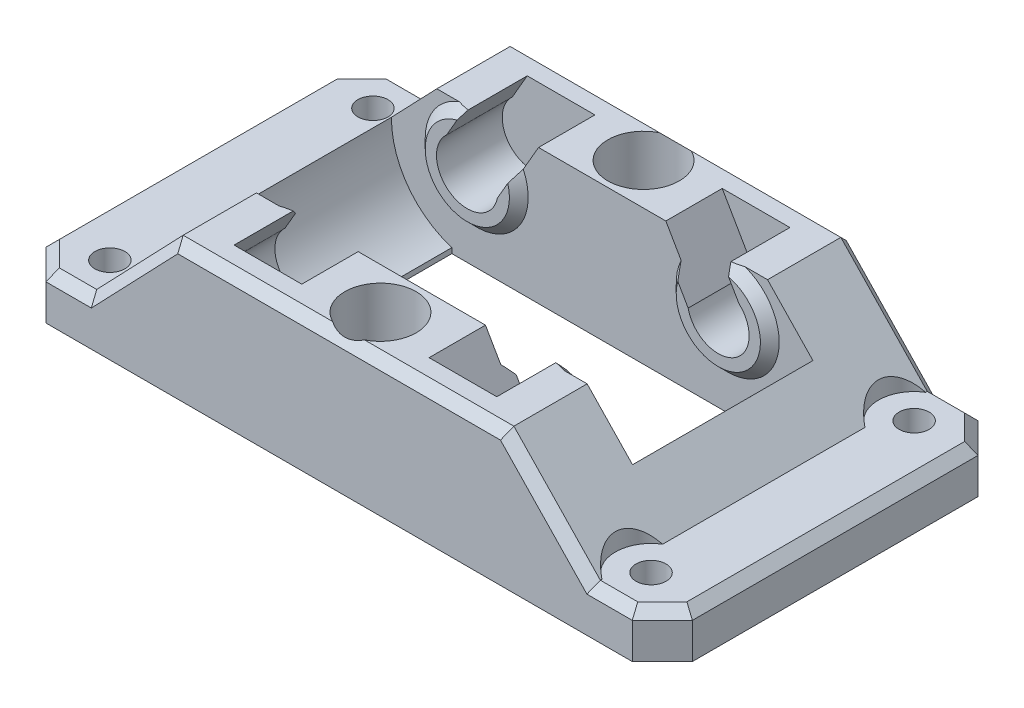
SolidWorks part; units mm, degrees
material "ABS"
ref_plane "Front Plane" through (0, 0, 0) normal (0, 0, 1) x (1, 0, 0)
ref_plane "Top Plane" through (0, 0, 0) normal (0, 1, 0) x (1, 0, 0)
ref_plane "Right Plane" through (0, 0, 0) normal (1, 0, 0) x (0, 0, -1)
sketch "Sketch1" plane through (0, 0, 0) normal (0, 1, 0) x (1, 0, 0)
  line L0 (-39, -23) -> (-43, -19)
  line L1 (39, 23) -> (-39, 23)
  line L2 (43, 19) -> (43, -19)
  line L3 (39, -23) -> (-39, -23)
  line L4 (-43, 19) -> (-43, -19)
  line L5 (43, 23) -> (-43, -23) construction
  line L6 (43, -23) -> (-43, 23) construction
  line L7 (-39, 23) -> (-43, 19)
  line L8 (43, 19) -> (39, 23)
  line L9 (43, -19) -> (39, -23)
  line L11 (36, 17.5) -> (-36, 17.5) construction
  line L12 (36, 17.5) -> (36, -17.5) construction
  line L13 (36, -17.5) -> (-36, -17.5) construction
  line L14 (-36, 17.5) -> (-36, -17.5) construction
  line L15 (36, 17.5) -> (-36, -17.5) construction
  line L16 (36, -17.5) -> (-36, 17.5) construction
  line L17 (20, 12) -> (-20, 12)
  line L18 (20, 12) -> (20, -12)
  line L19 (20, -12) -> (-20, -12)
  line L20 (-20, 12) -> (-20, -12)
  line L21 (20, 12) -> (-20, -12) construction
  line L22 (20, -12) -> (-20, 12) construction
  circle A0 centre (-36, 17.5) radius 2
  circle A1 centre (0, 17.5) radius 2
  circle A2 centre (36, 17.5) radius 2
  circle A3 centre (36, -17.5) radius 2
  circle A4 centre (0, -17.5) radius 2
  circle A5 centre (-36, -17.5) radius 2
  point P0 (0, 0)
  point P14 (0, 0)
  point P27 (0, 0)
  dimension "D9" = 4
  dimension "D10" = 4
  dimension "D11" = 4
  dimension "D12" = 4
  dimension "D13" = 4
  dimension "D14" = 4
  dimension "D1" = 46
  dimension "D2" = 86
  dimension "D3" = 35
  dimension "D4" = 72
  dimension "D15" = 24
  dimension "D16" = 40
extrude "Boss-Extrude1" add sketch "Sketch1" along normal blind 6
sketch "Sketch2" plane through (0, 0, 23) normal (0, 0, 1) x (1, 0, 0)
  line L0 (-33.5, 6) -> (-22, 18)
  line L1 (-39, 6) -> (39, 6) construction
  line L2 (-22, 18) -> (22, 18)
  line L3 (22, 18) -> (33.5, 6)
  line L4 (33.5, 6) -> (-33.5, 6)
  line L5 (0, 0) -> (0, 18) construction
  dimension "D1" = 67
  dimension "D2" = 33.5
  dimension "D3" = 12
  dimension "D4" = 44
extrude "Boss-Extrude2" add sketch "Sketch2" against normal up to surface (11 mm away) up to face at (0, 3, 12)
sketch "Sketch3" plane through (0, 0, -23) normal (0, 0, -1) x (-1, 0, 0)
  line L0 (-33.5, 6) -> (-22, 18)
  line L1 (-22, 18) -> (22, 18)
  line L2 (22, 18) -> (33.5, 6)
  line L3 (33.5, 6) -> (-33.5, 6)
extrude "Boss-Extrude3" add sketch "Sketch3" against normal up to surface (11 mm away) up to face at (0, 3, -12)
sketch "Sketch4" plane through (0, 0, 12) normal (0, 0, -1) x (-1, 0, 0)
  line L0 (-20, 6) -> (-20, 0) construction
  line L1 (-33.5, 6) -> (-22, 18) construction
  line L2 (39, 0) -> (-39, 0) construction
  line L3 (20, 0) -> (-20, 0) construction
  line L4 (0, 0) -> (0, 24.46) construction
  circle A0 centre (-16.6968, 11.55) radius 11.3417
  circle A1 centre (16.6968, 11.55) radius 11.3417
  point P2 (-20, 0.7)
  point P7 (-28.0375, 11.7)
  dimension "D1" = 0.7
  dimension "D2" = 11.7
  dimension "D3" = 11.55
extrude "Cut-Extrude1" cut sketch "Sketch4" along normal up to surface (24 mm away) up to face at (0, 7.5, -12)
sketch "Sketch5" plane through (0, 0, 12) normal (0, 0, -1) x (-1, 0, 0)
  line L0 (-26.5878, 6) -> (-33.5, 6)
  line L1 (-33.5, 6) -> (-28.0375, 11.7)
  line L2 (-33.5, 6) -> (-22, 18) construction
  line L3 (0, 0) -> (0, 27.4998) construction
  line L4 (33.5, 6) -> (28.0375, 11.7)
  line L5 (26.5878, 6) -> (33.5, 6)
  arc A0 (-28.0375, 11.7) -> (-26.5878, 6) centre (-16.6968, 11.55) ccw
  arc A1 (28.0375, 11.7) -> (26.5878, 6) centre (16.6968, 11.55) cw
extrude "Boss-Extrude4" add sketch "Sketch5" along normal up to surface (24 mm away) up to face at (0, 6.0126, -12)
ref_plane "Plane1" through (0, 0, 19.5) normal (0, 0, 1) x (1, 0, 0)
sketch "Sketch7" plane through (0, 0, 19.5) normal (0, 0, 1) x (1, 0, 0)
  line L0 (17.4762, 18) -> (19.4419, 14.5954)
  line L1 (22, 18) -> (-22, 18) construction
  line L2 (8.4696, 18) -> (12.6869, 10.6954)
  line L3 (0, 0) -> (0, 18) construction
  line L4 (16.6968, 11.55) -> (11.1898, 21.0884) construction
  line L5 (17.4762, 18) -> (8.4696, 18)
  line L6 (-8.4696, 18) -> (-12.6869, 10.6954)
  line L7 (-17.4762, 18) -> (-8.4696, 18)
  line L8 (-17.4762, 18) -> (-19.4419, 14.5954)
  arc A0 (12.6869, 10.6954) -> (19.4419, 14.5954) centre (16.6968, 11.55) ccw
  arc A1 (-12.6869, 10.6954) -> (-19.4419, 14.5954) centre (-16.6968, 11.55) cw
  dimension "D1" = 8.2
  dimension "D2" = 30
  dimension "D3" = 3.9
  dimension "D4" = 7.8
extrude "Cut-Extrude2" cut sketch "Sketch7" against normal blind 39
sketch "Sketch8" plane through (0, 0, 12) normal (0, 0, -1) x (-1, 0, 0)
  line L0 (-19.4419, 14.5954) -> (-18.065, 16.9803)
  line L1 (-17.4762, 18) -> (-19.4419, 14.5954) construction
  line L2 (-12.6869, 10.6954) -> (-11.31, 13.0803)
  line L3 (0, 0) -> (0, 18) construction
  line L4 (20, 0) -> (-20, 0) construction
  line L5 (-8.4696, 18) -> (8.4696, 18) construction
  line L6 (12.6869, 10.6954) -> (11.31, 13.0803)
  line L7 (19.4419, 14.5954) -> (18.065, 16.9803)
  arc A0 (-19.4419, 14.5954) -> (-12.6869, 10.6954) centre (-16.6968, 11.55) ccw
  arc A1 (-18.065, 16.9803) -> (-11.31, 13.0803) centre (-16.6968, 11.55) ccw
  arc A2 (-19.4419, 14.5954) -> (-12.6869, 10.6954) centre (-16.6968, 11.55) ccw construction
  circle A3 centre (-16.6968, 11.55) radius 4.1 construction
  circle A4 centre (-16.6968, 11.55) radius 5.6 construction
  arc A5 (18.065, 16.9803) -> (11.31, 13.0803) centre (16.6968, 11.55) cw
  arc A6 (19.4419, 14.5954) -> (12.6869, 10.6954) centre (16.6968, 11.55) cw
  dimension "D1" = 1.5
extrude "Boss-Extrude5" add sketch "Sketch8" along normal blind 1.25
mirror "Mirror5" about plane through (0, 0, 0) normal (0, 0, 1) of "Boss-Extrude5"
chamfer "Chamfer2" distance 1.25 angle 45 4 edges at (19.4968, 6.7003, 12) (-19.4968, 6.7003, 12) (19.4968, 6.7003, -12) (-19.4968, 6.7003, -12)
chamfer "Chamfer3" distance 1.25 angle 45 16 edges at (0, 18, -23) (27.75, 12, -23) (36.25, 6, -23) (41, 6, -21) (43, 6, 0) (41, 6, 21) (36.25, 6, 23) (27.75, 12, 23) (0, 18, 23) (-27.75, 12, 23) (-36.25, 6, 23) (-41, 6, 21) (-43, 6, 0) (-41, 6, -21) (-27.75, 12, -23) (-36.25, 6, -23)
sketch "Sketch9" plane through (0, 6, 0) normal (0, 1, 0) x (1, 0, 0)
  circle A0 centre (-36, 17.5) radius 4.75
  circle A1 centre (-36, -17.5) radius 4.75
  circle A2 centre (36, -17.5) radius 4.75
  circle A3 centre (36, 17.5) radius 4.75
  circle A4 centre (0, 17.5) radius 4.75
  circle A5 centre (0, -17.5) radius 4.75
  dimension "D1" = 9.5
  dimension "D2" = 9.5
  dimension "D3" = 9.5
  dimension "D4" = 9.5
  dimension "D5" = 9.5
  dimension "D6" = 9.5
extrude "Cut-Extrude3" cut sketch "Sketch9" along normal through all
